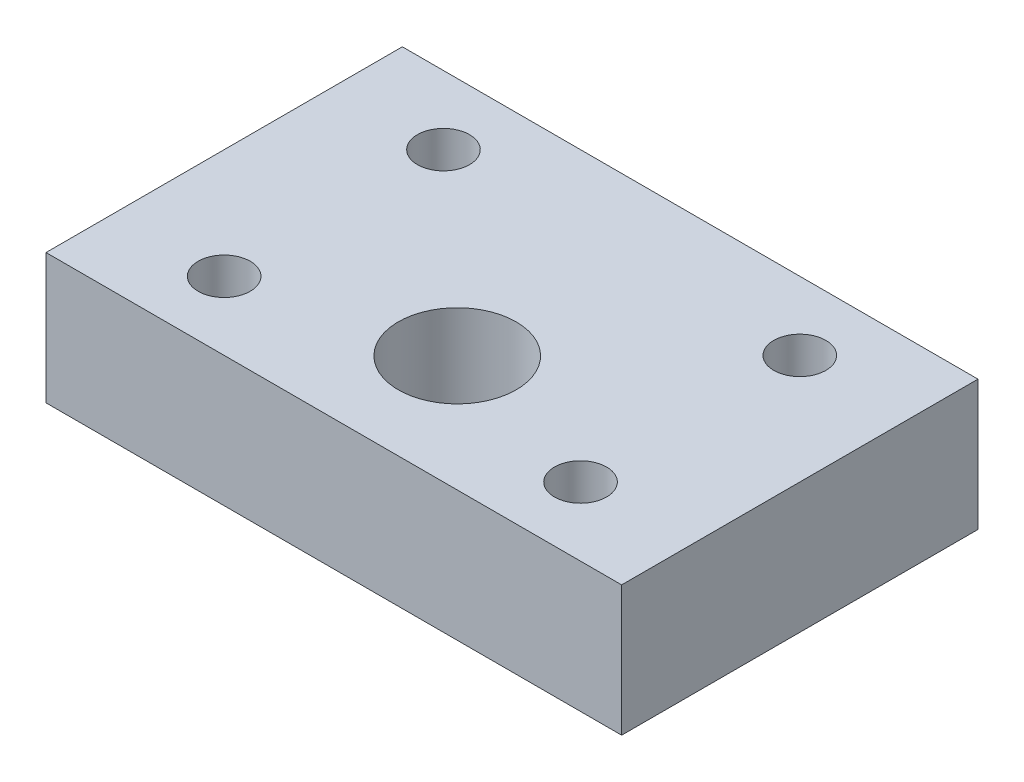
SolidWorks part; units mm, degrees
ref_plane "前视基准面" through (0, 0, 0) normal (0, 0, 1) x (1, 0, 0)
ref_plane "上视基准面" through (0, 0, 0) normal (0, 1, 0) x (1, 0, 0)
ref_plane "右视基准面" through (0, 0, 0) normal (1, 0, 0) x (0, 0, -1)
sketch "草图1" plane through (0, 0, 0) normal (0, 1, 0) x (1, 0, 0)
  line L1 (-21, 13) -> (21, 13)
  line L2 (-21, 13) -> (-21, -13)
  line L3 (-21, -13) -> (21, -13)
  line L4 (21, 13) -> (21, -13)
  line L5 (-21, 13) -> (21, -13) construction
  line L6 (-21, -13) -> (21, 13) construction
  point P0 (0, 0)
  dimension "D1" = 42
  dimension "D2" = 26
extrude "凸台-拉伸1" add sketch "草图1" along normal blind 9.5
sketch "草图6" plane through (0, 0, 0) normal (0, -1, 0) x (1, 0, 0)
  line L0 (-21, -13) -> (-21, 13) construction
  circle A0 centre (0.53, 4.5262) radius 4.3
  dimension "D1" = 8.6
  dimension "D2" = 21.53
extrude "切除-拉伸1" cut sketch "草图6" against normal through all
sketch "草图8" plane through (0, 0, 0) normal (0, -1, 0) x (1, 0, 0)
  line L0 (-21, 13) -> (21, 13) construction
  line L1 (21, -13) -> (-21, -13) construction
  line L2 (-21, -13) -> (-21, 13) construction
  line L3 (21, 13) -> (21, -13) construction
  circle A0 centre (-13, 8) radius 1.9
  circle A1 centre (13, 8) radius 1.9
  circle A2 centre (-13, -8) radius 1.9
  circle A3 centre (13, -8) radius 1.9
  dimension "D1" = 3.8
  dimension "D2" = 5
  dimension "D3" = 5
  dimension "D4" = 5
  dimension "D5" = 5
  dimension "D6" = 8
  dimension "D7" = 8
  dimension "D8" = 8
  dimension "D9" = 8
extrude "切除-拉伸3" cut sketch "草图8" against normal through all
